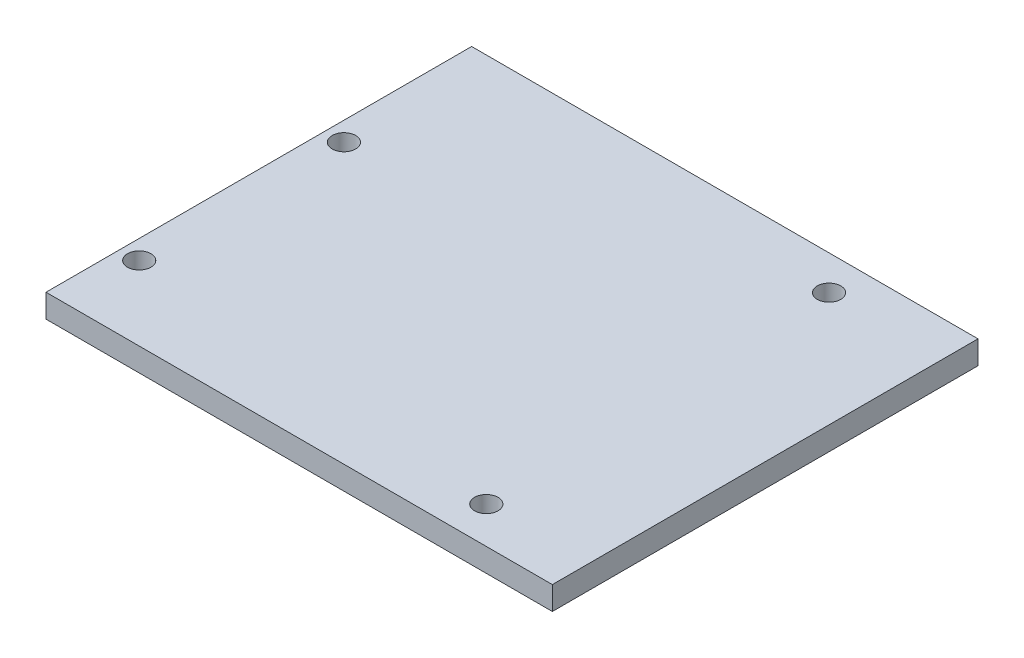
SolidWorks part; units mm, degrees
ref_plane "Front Plane" through (0, 0, 0) normal (0, 0, 1) x (1, 0, 0)
ref_plane "Top Plane" through (0, 0, 0) normal (0, 1, 0) x (1, 0, 0)
ref_plane "Right Plane" through (0, 0, 0) normal (1, 0, 0) x (0, 0, -1)
sketch "Sketch1" plane through (0, 0, 0) normal (0, 1, 0) x (1, 0, 0)
  line L1 (34.5, 29) -> (-34.5, 29)
  line L2 (34.5, 29) -> (34.5, -29)
  line L3 (34.5, -29) -> (-34.5, -29)
  line L4 (-34.5, 29) -> (-34.5, -29)
  line L5 (34.5, 29) -> (-34.5, -29) construction
  line L6 (34.5, -29) -> (-34.5, 29) construction
  point P0 (0, 0)
  dimension "D1" = 58
  dimension "D2" = 69
extrude "Boss-Extrude1" add sketch "Sketch1" along normal blind 3.18 contours L2 L1 L4 L3
sketch "Sketch2" plane through (0, 3.18, 0) normal (0, 1, 0) x (1, 0, 0)
  line L0 (34.5, -29) -> (34.5, 29) construction
  line L1 (-34.5, -29) -> (34.5, -29) construction
  line L2 (20.5, -24) -> (20.5, 24.3) construction
  circle A0 centre (-31.9, 9) radius 1.6
  circle A1 centre (-31.9, -18.9) radius 1.6
  circle A2 centre (18.9, 24.3) radius 1.6
  circle A3 centre (20.5, -24) radius 1.6
  dimension "D1" = 3.2
  dimension "D2" = 50.8
  dimension "D3" = 27.9
  dimension "D7" = 5.1
  dimension "D4" = 48.3
  dimension "D5" = 14
  dimension "D6" = 5
extrude "Cut-Extrude1" cut sketch "Sketch2" against normal through all
sketch "Sketch3" [suppressed] plane through (0, 0, 0) normal (0, -1, 0) x (1, 0, 0)
  line L0 (-50, 50) -> (50, 50) construction
  line L1 (-5, 33.5) -> (8, 33.5)
  line L2 (-5, 33.5) -> (-5, 21.5)
  line L3 (-5, 21.5) -> (8, 21.5)
  line L4 (8, 33.5) -> (8, 21.5)
  line L5 (-5, 33.5) -> (8, 21.5) construction
  line L6 (-5, 21.5) -> (8, 33.5) construction
  line L7 (50, 50) -> (50, -50) construction
  point P0 (1.5, 27.5)
  dimension "D1" = 12
  dimension "D2" = 13
  dimension "D3" = 16.5
  dimension "D4" = 42
extrude "Cut-Extrude3" [suppressed] cut sketch "Sketch3" against normal up to surface (3 mm away) contours L3 L4 L1 L2 up to face at (20.5, 3.18, 25.6)
